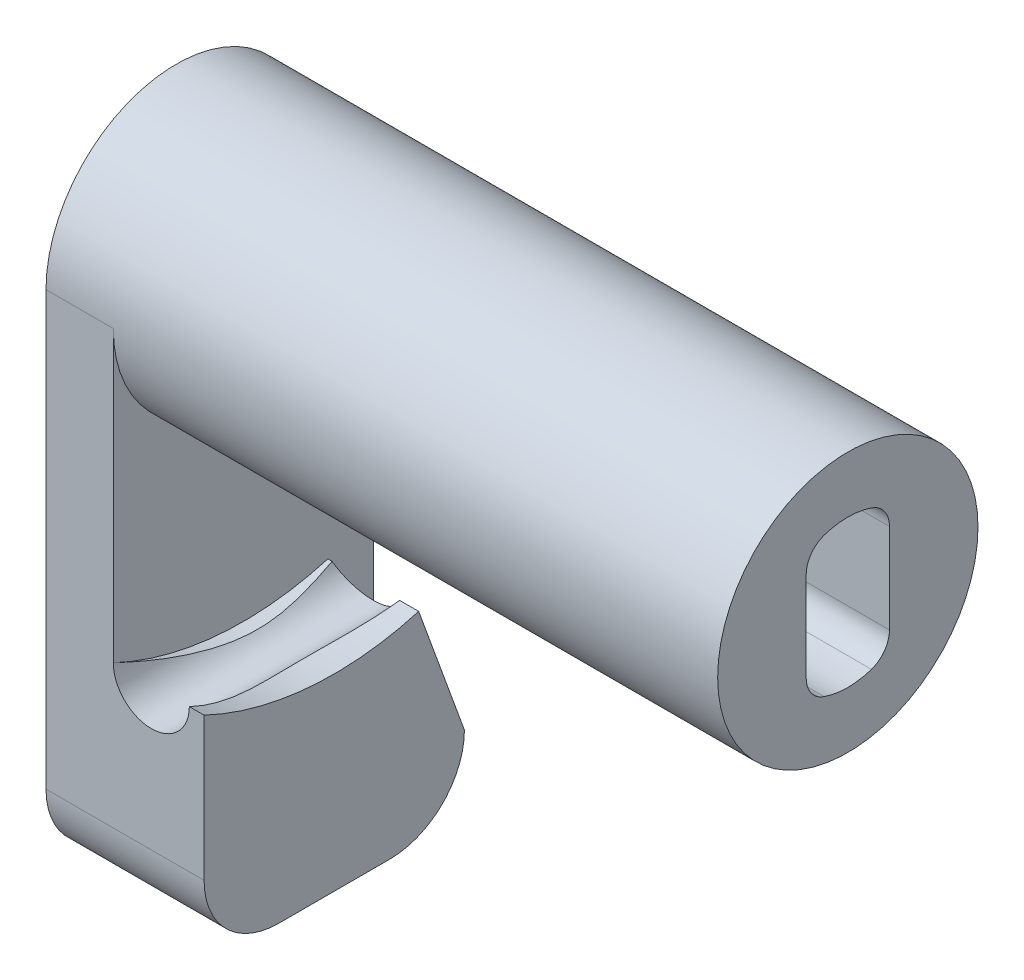
SolidWorks part; units mm, degrees
material "ABS"
ref_plane "Front Plane" through (0, 0, 0) normal (1, 0, 0) x (0, 1, 0)
ref_plane "Top Plane" through (0, 0, 0) normal (0, 0, 1) x (0, 1, 0)
ref_plane "Right Plane" through (0, 0, 0) normal (0, 1, 0) x (-1, 0, 0)
sketch "Sketch1" plane through (0, 0, 0) normal (1, 0, 0) x (0, 1, 0)
  circle A2 centre (0, 0) radius 8.7376
  dimension "D3" = 17.4752
extrude "Boss-Extrude1" add sketch "Sketch1" along normal blind 45.085 contours A2 region at (0, 0, 0)
sketch "Sketch10" plane through (0, 0, 0) normal (-1, 0, 0) x (0, -1, 0)
  line L0 (0, 8.7376) -> (34.036, 8.7376)
  line L2 (34.036, 8.7376) -> (34.036, -8.7376)
  line L3 (34.036, -8.7376) -> (0, -8.7376)
  circle A0 centre (0, 0) radius 8.7376 construction
  arc A2 (0, 8.7376) -> (0, -8.7376) centre (0, 0) cw
  dimension "D1" = 34.036
extrude "Boss-Extrude3" add sketch "Sketch10" against normal blind 4.516 contours L0 A2 L3 L2 region at (0, -20.3793, 0)
fillet "Fillet2" radius 5 2 edges at (2.258, -34.036, 8.7376) (2.258, -34.036, -8.7376)
sketch "Sketch14" [suppressed] plane through (0, 0, 0) normal (-1, 0, 0) x (0, 0, 1)
  line L0 (0.5115, -3.4237) -> (0.3944, -4.0089)
  line L1 (0, 0) -> (0, -4.064) construction
  line L2 (0, 0) -> (0.5606, -3.4335) construction
  line L3 (0.6039, -3.4087) -> (0.9011, -3.9262)
  line L4 (-0.6903, -3.3922) -> (-1.0005, -3.9021)
  line L5 (-0.5983, -3.4096) -> (-0.4961, -3.9976)
  line L6 (-1.8089, -2.9515) -> (-2.2748, -3.3245)
  line L7 (-1.7284, -2.9994) -> (-1.8334, -3.5869)
  line L8 (-2.7093, -2.1549) -> (-3.2746, -2.346)
  line L9 (-2.65, -2.2273) -> (-2.9496, -2.7435)
  line L10 (-3.2829, -1.0983) -> (-3.8795, -1.0846)
  line L11 (-3.252, -1.1867) -> (-3.7101, -1.5692)
  line L12 (-3.4605, 0.0907) -> (-4.0165, 0.3077)
  line L13 (-3.4617, -0.0029) -> (-4.023, -0.2057)
  line L14 (-3.2208, 1.2689) -> (-3.669, 1.6629)
  line L15 (-3.2539, 1.1813) -> (-3.8507, 1.1827)
  line L16 (-2.5926, 2.2939) -> (-2.879, 2.8175)
  line L17 (-2.6537, 2.223) -> (-3.214, 2.4284)
  line L18 (-1.6517, 3.0423) -> (-1.7417, 3.6323)
  line L19 (-1.7333, 2.9965) -> (-2.1896, 3.3812)
  line L20 (-0.5115, 3.4237) -> (-0.3944, 4.0089)
  line L21 (-0.6039, 3.4087) -> (-0.9011, 3.9262)
  line L22 (0.6903, 3.3922) -> (1.0005, 3.9021)
  line L23 (0.5983, 3.4096) -> (0.4961, 3.9976)
  line L24 (1.8089, 2.9515) -> (2.2748, 3.3245)
  line L25 (1.7284, 2.9994) -> (1.8334, 3.5869)
  line L26 (2.7093, 2.1549) -> (3.2746, 2.346)
  line L27 (2.65, 2.2273) -> (2.9496, 2.7435)
  line L28 (3.2829, 1.0983) -> (3.8795, 1.0846)
  line L29 (3.252, 1.1867) -> (3.7101, 1.5692)
  line L30 (3.4605, -0.0907) -> (4.0165, -0.3077)
  line L31 (3.4617, 0.0029) -> (4.023, 0.2057)
  line L32 (3.2208, -1.2689) -> (3.669, -1.6629)
  line L33 (3.2539, -1.1813) -> (3.8507, -1.1827)
  line L34 (2.5926, -2.2939) -> (2.879, -2.8175)
  line L35 (2.6537, -2.223) -> (3.214, -2.4284)
  line L36 (1.6517, -3.0423) -> (1.7417, -3.6323)
  line L37 (1.7333, -2.9965) -> (2.1896, -3.3812)
  line L38 (-0.1032, -4.0627) -> (0, -4.064)
  line L39 (-1.4865, -3.7824) -> (-1.39, -3.8189)
  line L40 (-2.6905, -3.0459) -> (-2.6123, -3.1132)
  line L41 (-3.5195, -2.032) -> (-3.57, -1.942)
  line L42 (-4.0023, -0.7057) -> (-4.0189, -0.6039)
  line L43 (-4.0023, 0.7057) -> (-3.9831, 0.8071)
  line L44 (-3.5195, 2.032) -> (-3.4668, 2.1207)
  line L45 (-2.6123, 3.1132) -> (-2.5324, 3.1785)
  line L46 (-1.39, 3.8189) -> (-1.2926, 3.853)
  line L47 (0, 4.064) -> (0.1032, 4.0627)
  line L48 (1.39, 3.8189) -> (1.4865, 3.7824)
  line L49 (2.6123, 3.1132) -> (2.6905, 3.0459)
  line L50 (3.5195, 2.032) -> (3.57, 1.942)
  line L51 (4.0023, 0.7057) -> (4.0189, 0.6039)
  line L52 (4.0023, -0.7057) -> (3.9831, -0.8071)
  line L53 (3.5195, -2.032) -> (3.4668, -2.1207)
  line L54 (2.6123, -3.1132) -> (2.5324, -3.1785)
  line L55 (1.39, -3.8189) -> (1.2926, -3.853)
  arc A0 (0.3497, -4.0489) -> (0, -4.064) centre (0, 0) cw
  arc A1 (0.3497, -4.0489) -> (0.3944, -4.0089) centre (0.3454, -3.9991) ccw
  arc A2 (0.5115, -3.4237) -> (0.6039, -3.4087) centre (0.5606, -3.4335) cw
  arc A3 (0.4203, -4.0631) -> (0.3944, -4.0089) centre (0.4434, -4.0187) cw
  arc A4 (0.4203, -4.0631) -> (0.7372, -4.2116) centre (2.3016, -0.4608) ccw
  arc A6 (0.9562, -3.9499) -> (0.9011, -3.9262) centre (0.9445, -3.9013) cw
  arc A7 (0.9562, -3.9499) -> (1.2926, -3.853) centre (0, 0) ccw
  arc A8 (-1.0562, -3.9243) -> (-1.39, -3.8189) centre (0, 0) cw
  arc A9 (-1.0562, -3.9243) -> (-1.0005, -3.9021) centre (-1.0432, -3.8761) ccw
  arc A10 (-0.6903, -3.3922) -> (-0.5983, -3.4096) centre (-0.6476, -3.4182) cw
  arc A11 (-0.4524, -4.0387) -> (-0.4961, -3.9976) centre (-0.4468, -3.9891) cw
  arc A12 (-0.4524, -4.0387) -> (-0.1032, -4.0627) centre (0, 0) ccw
  arc A13 (-2.3347, -3.3264) -> (-2.6123, -3.1132) centre (0, 0) cw
  arc A14 (-2.3347, -3.3264) -> (-2.2748, -3.3245) centre (-2.306, -3.2855) ccw
  arc A15 (-1.8089, -2.9515) -> (-1.7284, -2.9994) centre (-1.7776, -2.9906) cw
  arc A16 (-1.8064, -3.6405) -> (-1.8334, -3.5869) centre (-1.7842, -3.5957) cw
  arc A17 (-1.8064, -3.6405) -> (-1.4865, -3.7824) centre (0, 0) ccw
  arc A18 (-3.3316, -2.3273) -> (-3.5195, -2.032) centre (0, 0) cw
  arc A19 (-3.3316, -2.3273) -> (-3.2746, -2.346) centre (-3.2906, -2.2987) ccw
  arc A20 (-2.7093, -2.1549) -> (-2.65, -2.2273) centre (-2.6933, -2.2022) cw
  arc A21 (-2.9426, -2.8031) -> (-2.9496, -2.7435) centre (-2.9064, -2.7686) cw
  arc A22 (-2.9426, -2.8031) -> (-2.6905, -3.0459) centre (0, 0) ccw
  arc A23 (-3.9267, -1.0475) -> (-4.0023, -0.7057) centre (0, 0) cw
  arc A24 (-3.9267, -1.0475) -> (-3.8795, -1.0846) centre (-3.8784, -1.0346) ccw
  arc A25 (-3.2829, -1.0983) -> (-3.252, -1.1867) centre (-3.284, -1.1483) cw
  arc A26 (-3.7238, -1.6276) -> (-3.7101, -1.5692) centre (-3.678, -1.6076) cw
  arc A27 (-3.7238, -1.6276) -> (-3.57, -1.942) centre (0, 0) ccw
  arc A28 (-4.0481, 0.3587) -> (-4.0023, 0.7057) centre (0, 0) cw
  arc A29 (-4.0481, 0.3587) -> (-4.0165, 0.3077) centre (-3.9983, 0.3543) ccw
  arc A30 (-3.4605, 0.0907) -> (-3.4617, -0.0029) centre (-3.4787, 0.0442) cw
  arc A31 (-4.0559, -0.2558) -> (-4.023, -0.2057) centre (-4.006, -0.2527) cw
  arc A32 (-4.0559, -0.2558) -> (-4.0189, -0.6039) centre (0, 0) ccw
  arc A33 (-3.6813, 1.7216) -> (-3.5195, 2.032) centre (0, 0) cw
  arc A34 (-3.6813, 1.7216) -> (-3.669, 1.6629) centre (-3.636, 1.7005) ccw
  arc A35 (-3.2208, 1.2689) -> (-3.2539, 1.1813) centre (-3.2538, 1.2313) cw
  arc A36 (-3.8988, 1.1468) -> (-3.8507, 1.1827) centre (-3.8509, 1.1327) cw
  arc A37 (-3.8988, 1.1468) -> (-3.9831, 0.8071) centre (0, 0) ccw
  arc A38 (-2.8705, 2.8769) -> (-2.6123, 3.1132) centre (0, 0) cw
  arc A39 (-2.8705, 2.8769) -> (-2.879, 2.8175) centre (-2.8352, 2.8415) ccw
  arc A40 (-2.5926, 2.2939) -> (-2.6537, 2.223) centre (-2.6365, 2.2699) cw
  arc A41 (-3.2715, 2.4111) -> (-3.214, 2.4284) centre (-3.2312, 2.3815) cw
  arc A42 (-3.2715, 2.4111) -> (-3.4668, 2.1207) centre (0, 0) ccw
  arc A43 (-1.7134, 3.6852) -> (-1.39, 3.8189) centre (0, 0) cw
  arc A44 (-1.7134, 3.6852) -> (-1.7417, 3.6323) centre (-1.6923, 3.6398) ccw
  arc A45 (-1.6517, 3.0423) -> (-1.7333, 2.9965) centre (-1.7011, 3.0348) cw
  arc A46 (-2.2495, 3.3846) -> (-2.1896, 3.3812) centre (-2.2218, 3.343) cw
  arc A47 (-2.2495, 3.3846) -> (-2.5324, 3.1785) centre (0, 0) ccw
  arc A48 (-0.3497, 4.0489) -> (0, 4.064) centre (0, 0) cw
  arc A49 (-0.3497, 4.0489) -> (-0.3944, 4.0089) centre (-0.3454, 3.9991) ccw
  arc A50 (-0.5115, 3.4237) -> (-0.6039, 3.4087) centre (-0.5606, 3.4335) cw
  arc A51 (-0.9562, 3.9499) -> (-0.9011, 3.9262) centre (-0.9445, 3.9013) cw
  arc A52 (-0.9562, 3.9499) -> (-1.2926, 3.853) centre (0, 0) ccw
  arc A53 (1.0562, 3.9243) -> (1.39, 3.8189) centre (0, 0) cw
  arc A54 (1.0562, 3.9243) -> (1.0005, 3.9021) centre (1.0432, 3.8761) ccw
  arc A55 (0.6903, 3.3922) -> (0.5983, 3.4096) centre (0.6476, 3.4182) cw
  arc A56 (0.4524, 4.0387) -> (0.4961, 3.9976) centre (0.4468, 3.9891) cw
  arc A57 (0.4524, 4.0387) -> (0.1032, 4.0627) centre (0, 0) ccw
  arc A58 (2.3347, 3.3264) -> (2.6123, 3.1132) centre (0, 0) cw
  arc A59 (2.3347, 3.3264) -> (2.2748, 3.3245) centre (2.306, 3.2855) ccw
  arc A60 (1.8089, 2.9515) -> (1.7284, 2.9994) centre (1.7776, 2.9906) cw
  arc A61 (1.8064, 3.6405) -> (1.8334, 3.5869) centre (1.7842, 3.5957) cw
  arc A62 (1.8064, 3.6405) -> (1.4865, 3.7824) centre (0, 0) ccw
  arc A63 (3.3316, 2.3273) -> (3.5195, 2.032) centre (0, 0) cw
  arc A64 (3.3316, 2.3273) -> (3.2746, 2.346) centre (3.2906, 2.2987) ccw
  arc A65 (2.7093, 2.1549) -> (2.65, 2.2273) centre (2.6933, 2.2022) cw
  arc A66 (2.9426, 2.8031) -> (2.9496, 2.7435) centre (2.9064, 2.7686) cw
  arc A67 (2.9426, 2.8031) -> (2.6905, 3.0459) centre (0, 0) ccw
  arc A68 (3.9267, 1.0475) -> (4.0023, 0.7057) centre (0, 0) cw
  arc A69 (3.9267, 1.0475) -> (3.8795, 1.0846) centre (3.8784, 1.0346) ccw
  arc A70 (3.2829, 1.0983) -> (3.252, 1.1867) centre (3.284, 1.1483) cw
  arc A71 (3.7238, 1.6276) -> (3.7101, 1.5692) centre (3.678, 1.6076) cw
  arc A72 (3.7238, 1.6276) -> (3.57, 1.942) centre (0, 0) ccw
  arc A73 (4.0481, -0.3587) -> (4.0023, -0.7057) centre (0, 0) cw
  arc A74 (4.0481, -0.3587) -> (4.0165, -0.3077) centre (3.9983, -0.3543) ccw
  arc A75 (3.4605, -0.0907) -> (3.4617, 0.0029) centre (3.4787, -0.0442) cw
  arc A76 (4.0559, 0.2558) -> (4.023, 0.2057) centre (4.006, 0.2527) cw
  arc A77 (4.0559, 0.2558) -> (4.0189, 0.6039) centre (0, 0) ccw
  arc A78 (3.6813, -1.7216) -> (3.5195, -2.032) centre (0, 0) cw
  arc A79 (3.6813, -1.7216) -> (3.669, -1.6629) centre (3.636, -1.7005) ccw
  arc A80 (3.2208, -1.2689) -> (3.2539, -1.1813) centre (3.2538, -1.2313) cw
  arc A81 (3.8988, -1.1468) -> (3.8507, -1.1827) centre (3.8509, -1.1327) cw
  arc A82 (3.8988, -1.1468) -> (3.9831, -0.8071) centre (0, 0) ccw
  arc A83 (2.8705, -2.8769) -> (2.6123, -3.1132) centre (0, 0) cw
  arc A84 (2.8705, -2.8769) -> (2.879, -2.8175) centre (2.8352, -2.8415) ccw
  arc A85 (2.5926, -2.2939) -> (2.6537, -2.223) centre (2.6365, -2.2699) cw
  arc A86 (3.2715, -2.4111) -> (3.214, -2.4284) centre (3.2312, -2.3815) cw
  arc A87 (3.2715, -2.4111) -> (3.4668, -2.1207) centre (0, 0) ccw
  arc A88 (1.7134, -3.6852) -> (1.39, -3.8189) centre (0, 0) cw
  arc A89 (1.7134, -3.6852) -> (1.7417, -3.6323) centre (1.6923, -3.6398) ccw
  arc A90 (1.6517, -3.0423) -> (1.7333, -2.9965) centre (1.7011, -3.0348) cw
  arc A91 (2.2495, -3.3846) -> (2.1896, -3.3812) centre (2.2218, -3.343) cw
  arc A92 (2.2495, -3.3846) -> (2.5324, -3.1785) centre (0, 0) ccw
  point P207 (0, 0)
  dimension "D1" = 4.064
  dimension "D2" = 0.05
  dimension "D3" = 0.05
  dimension "D4" = 0.04
  dimension "D5" = 18
  dimension "D6" = 0.5968
  dimension "D8" = 0.35
sketch "Sketch15" plane through (4.516, 0, 0) normal (1, 0, 0) x (0, 1, 0)
  line L1 (-29.036, 8.7376) -> (-18.796, 8.7376)
  line L2 (-18.796, 8.7376) -> (-18.796, -5.0105)
  line L3 (0, 8.7376) -> (-29.036, 8.7376) construction
  line L4 (-29.036, -8.7376) -> (-18.796, -5.0105)
  line L5 (-34.036, 3.7376) -> (-34.036, -3.7376) construction
  line L6 (-34.036, 3.7376) -> (-34.036, -3.7376)
  line L13 (0, 8.7376) -> (-29.036, 8.7376)
  line L14 (-34.036, 3.7376) -> (-34.036, -3.7376)
  line L15 (-29.036, -8.7376) -> (0, -8.7376)
  line L17 (-34.036, 3.7376) -> (-34.036, -3.7376)
  arc A0 (-29.036, 8.7376) -> (-34.036, 3.7376) centre (-29.036, 3.7376) ccw construction
  arc A1 (-34.036, -3.7376) -> (-29.036, -8.7376) centre (-29.036, -3.7376) ccw construction
  arc A2 (-29.036, 8.7376) -> (-34.036, 3.7376) centre (-29.036, 3.7376) ccw
  arc A3 (-34.036, -3.7376) -> (-29.036, -8.7376) centre (-29.036, -3.7376) ccw
  arc A7 (-29.036, 8.7376) -> (-34.036, 3.7376) centre (-29.036, 3.7376) ccw
  arc A8 (-34.036, -3.7376) -> (-29.036, -8.7376) centre (-29.036, -3.7376) ccw
  arc A9 (0, 8.7376) -> (0, -8.7376) centre (0, 0) ccw
  arc A10 (-29.036, 8.7376) -> (-34.036, 3.7376) centre (-29.036, 3.7376) ccw
  arc A11 (-34.036, -3.7376) -> (-29.036, -8.7376) centre (-29.036, -3.7376) ccw
  arc A12 (0, 8.7376) -> (0, -8.7376) centre (0, 0) ccw
  line M2 (0, 8.7376) -> (-29.036, 8.7376)
  arc M3 (-29.036, 8.7376) -> (-34.036, 3.7376) centre (-29.036, 3.7376) ccw
  line M4 (-34.036, 3.7376) -> (-34.036, -3.7376)
  arc M5 (-34.036, -3.7376) -> (-29.036, -8.7376) centre (-29.036, -3.7376) ccw
  dimension "D1" = 15.24
  dimension "D3" = 20
  dimension "D2" = 0
extrude "Boss-Extrude4" add sketch "Sketch15" along normal blind 6.096 contours M2 M3 M4 M5 region at (4.516, -26.4604, 0.6047)
sketch "Sketch21" plane through (10.612, 0, 0) normal (1, 0, 0) x (0, 1, 0)
  line L2 (-18.796, -8.7376) -> (-18.796, 8.7376)
  line L4 (-29.036, 8.7376) -> (-18.796, 8.7376) construction
  line L5 (-19.431, -8.7376) -> (-18.796, -8.7376)
  line L6 (-18.796, 8.7376) -> (-18.796, -5.0105) construction
  line L8 (-29.036, -8.7376) -> (0, -8.7376) construction
  line L14 (-18.796, -8.7376) -> (-18.796, 8.7376) construction
  line L20 (-18.796, 8.7376) -> (-29.036, 8.7376)
  arc A2 (-19.431, -8.7376) -> (-19.431, 8.7376) centre (-1.0855, 0) cw
  dimension "D4" = 20.32
  dimension "D2" = 0.635
  dimension "D3" = 0.635
extrude "Cut-Extrude8" cut sketch "Sketch21" against normal up to surface (6.096 mm away) contours A2 L2 region at (10.612, -19.8652, 0) up to face at (4.516, -15.0731, -1.0021)
sketch "Sketch22" plane through (45.085, 0, 0) normal (1, 0, 0) x (0, 1, 0)
  line L7 (-4.0897, -2.794) -> (4.0897, 2.794) construction
  line L8 (-4.0897, 2.794) -> (4.0897, -2.794) construction
  line L11 (-4.0897, -2.794) -> (4.0897, -2.794)
  line L13 (-4.0897, 2.794) -> (4.0897, 2.794)
  line L15 (-4.0897, -2.794) -> (4.0897, 2.794) construction
  line L16 (-4.0897, 2.794) -> (4.0897, -2.794) construction
  arc A3 (-4.0897, 2.794) -> (-4.0897, -2.794) centre (0, 0) ccw
  arc A4 (4.0897, -2.794) -> (4.0897, 2.794) centre (0, 0) ccw
  dimension "D2" = 9.906
  dimension "D3" = 5.588
extrude "Cut-Extrude10" cut sketch "Sketch22" against normal blind 12.192
fillet "Fillet11" radius 1.778 4 edges at (38.989, 4.0897, -2.794) (38.989, 4.0897, 2.794) (38.989, -4.0897, -2.794) (38.989, -4.0897, 2.794)
sketch "Sketch25" plane through (0, 0, -8.7376) normal (0, 0, -1) x (1, 0, 0)
  line L3 (4.516, 29.036) -> (4.516, 0) construction
  line L4 (4.516, 19.431) -> (10.612, 19.431) construction
  circle A0 centre (7.0687, 19.431) radius 2.5527
  dimension "D1" = 5.1054
extrude "Cut-Extrude14" cut sketch "Sketch25" against normal through all
sketch "Sketch26" plane through (0, 0, 0) normal (-1, 0, 0) x (0, -1, 0)
  line L1 (3.7411, 1.5875) -> (5.3921, 1.5875)
  line L2 (3.7411, 1.5875) -> (3.7411, -1.5875) construction
  line L3 (3.7411, -1.5875) -> (5.3921, -1.5875)
  line L4 (5.3921, 1.5875) -> (5.3921, -1.5875)
  arc A0 (3.7411, 1.5875) -> (3.7411, -1.5875) centre (0, 0) ccw
  point P7 (0, 0)
  dimension "D1" = 8.128
  dimension "D2" = 3.175
  dimension "D3" = 1.651
extrude "Cut-Extrude15" cut sketch "Sketch26" against normal blind 21.59
fillet "Fillet12" radius 0.3969 4 edges at (10.795, -3.7411, 1.5875) (10.795, -5.3921, 1.5875) (10.795, -3.7411, -1.5875) (10.795, -5.3921, -1.5875)
